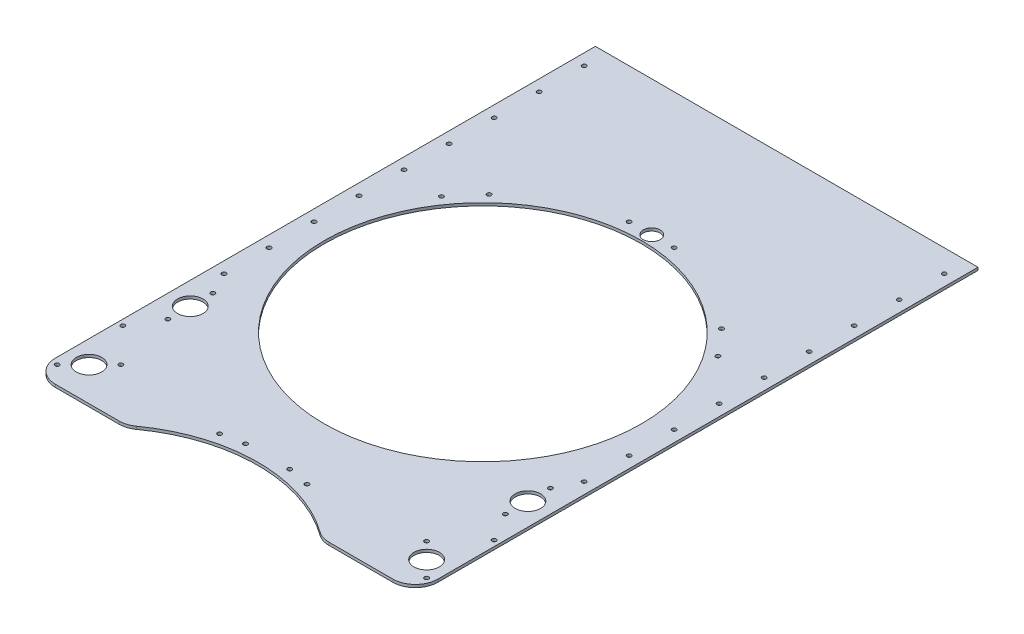
SolidWorks part; units mm, degrees
material "6063-T1"
ref_plane "Front Plane" through (0, 0, 0) normal (0, 0, 1) x (1, 0, 0)
ref_plane "Top Plane" through (0, 0, 0) normal (0, 1, 0) x (1, 0, 0)
ref_plane "Right Plane" through (0, 0, 0) normal (1, 0, 0) x (0, 0, -1)
sketch "Sketch1" plane through (0, 0, 0) normal (0, 1, 0) x (1, 0, 0)
  line L1 (-215.9, 342.9) -> (215.9, 342.9)
  line L2 (-215.9, 342.9) -> (-215.9, -342.9)
  line L3 (-215.9, -342.9) -> (215.9, -342.9)
  line L4 (215.9, 342.9) -> (215.9, -342.9)
  line L5 (-215.9, 342.9) -> (215.9, -342.9) construction
  line L6 (-215.9, -342.9) -> (215.9, 342.9) construction
  point P0 (0, 0)
  dimension "D1" = 431.8
  dimension "D2" = 685.8
extrude "Boss-Extrude1" add sketch "Sketch1" along normal blind 3.175
sketch "Sketch2" plane through (0, 3.175, 0) normal (0, 1, 0) x (1, 0, 0)
  line L0 (0, -342.9) -> (0, 342.9) construction
  line L1 (-215.9, -342.9) -> (215.9, -342.9) construction
  line L2 (215.9, 342.9) -> (-215.9, 342.9) construction
  line L3 (-215.9, 342.9) -> (-215.9, -342.9) construction
  line L4 (-208.4605, -322.7605) -> (-190.5, -304.8) construction
  line L5 (-193.1461, -304.8) -> (-215.9, -304.8) construction
  circle A0 centre (-190.5, -304.8) radius 14.3129
  circle A1 centre (-190.5, -190.5) radius 14.3129
  circle A3 centre (190.5, -190.5) radius 14.3129
  circle A4 centre (190.5, -190.5) radius 25.4 construction
  circle A5 centre (-190.5, -190.5) radius 25.4 construction
  circle A6 centre (190.5, -215.9) radius 2.3813
  circle A7 centre (190.5, -165.1) radius 2.3813
  circle A8 centre (-190.5, -215.9) radius 2.3813
  circle A9 centre (-190.5, -165.1) radius 2.3813
  circle A10 centre (-190.5, -304.8) radius 25.4 construction
  circle A11 centre (-208.4605, -322.7605) radius 2.3813
  circle A15 centre (-172.5395, -286.8395) radius 2.3813
  circle A16 centre (172.5395, -286.8395) radius 2.3813
  circle A17 centre (208.4605, -322.7605) radius 2.3813
  circle A18 centre (190.5, -304.8) radius 14.3129
  point P33 (-190.5, -304.8)
  point P34 (-190.5, -304.8)
  dimension "D1" = 28.6258
  dimension "D2" = 28.6258
  dimension "D6" = 50.8
  dimension "D7" = 50.8
  dimension "D8" = 4.7625
  dimension "D9" = 4.7625
  dimension "D10" = 4.7625
  dimension "D11" = 4.7625
  dimension "D12" = 50.8
  dimension "D13" = 4.7625
  dimension "D3" = 38.1
  dimension "D4" = 114.3
  dimension "D5" = 25.4
  dimension "D15" = 45
  dimension "D14" = 2
extrude "Cut-Extrude1" cut sketch "Sketch2" against normal through all
sketch "Sketch3" plane through (0, 0, 0) normal (0, -1, 0) x (-1, 0, 0)
  line L1 (29.8706, 270.2084) -> (-24.7394, 270.2084)
  line L2 (29.8706, 270.2084) -> (29.8706, 216.2334)
  line L3 (29.8706, 216.2334) -> (-24.7394, 216.2334)
  line L4 (-24.7394, 270.2084) -> (-24.7394, 216.2334)
  line L5 (29.8706, 270.2084) -> (-24.7394, 216.2334) construction
  line L6 (29.8706, 216.2334) -> (-24.7394, 270.2084) construction
  point P0 (2.5656, 243.2209)
  dimension "D1" = 53.975
  dimension "D2" = 54.61
extrude "Boss-Extrude2" [suppressed] add sketch "Sketch3" along normal blind 203.2
fillet "Fillet1" [suppressed] radius 20.32
sketch "Sketch4" [suppressed] plane through (0, -203.2, 0) normal (0, -1, 0) x (-1, 0, 0)
  line L0 (-24.7394, 216.2334) -> (29.8706, 216.2334) construction
  line L1 (26.6956, 267.0334) -> (-21.5644, 267.0334)
  line L2 (26.6956, 267.0334) -> (26.6956, 219.4084)
  line L3 (26.6956, 219.4084) -> (-21.5644, 219.4084)
  line L4 (-21.5644, 267.0334) -> (-21.5644, 219.4084)
  line L5 (26.6956, 267.0334) -> (-21.5644, 219.4084) construction
  line L6 (26.6956, 219.4084) -> (-21.5644, 267.0334) construction
  line L7 (29.8706, 270.2084) -> (-24.7394, 270.2084) construction
  line L8 (29.8706, 216.2334) -> (29.8706, 270.2084) construction
  line L9 (-24.7394, 270.2084) -> (-24.7394, 216.2334) construction
  point P0 (2.5656, 243.2209)
  dimension "D1" = 3.175
  dimension "D2" = 3.175
  dimension "D3" = 3.175
  dimension "D4" = 3.175
extrude "Cut-Extrude2" [suppressed] cut sketch "Sketch4" against normal blind 203.2
sketch "Sketch5" [suppressed] plane through (-29.8706, 0, 0) normal (-1, 0, 0) x (0, 0, 1)
  line L0 (-216.2334, -203.2) -> (-216.2334, 0) construction
  line L1 (-216.2334, -203.2) -> (-270.2084, -203.2) construction
  circle A0 centre (-243.2209, -184.15) radius 14.2875
  dimension "D1" = 28.575
  dimension "D2" = 26.9875
  dimension "D3" = 19.05
extrude "Cut-Extrude3" [suppressed] cut sketch "Sketch5" against normal blind 203.2
sketch "Sketch6" plane through (0, 3.175, 0) normal (0, 1, 0) x (1, 0, 0)
  circle A0 centre (0, -50.8) radius 179.07
  dimension "D1" = 358.14
  dimension "D2" = 50.8
extrude "Cut-Extrude4" cut sketch "Sketch6" against normal through all
sketch "Sketch8" plane through (0, 3.175, 0) normal (0, 1, 0) x (1, 0, 0)
  circle A0 centre (0, 139.7) radius 9.525
  circle A2 centre (0, 139.7) radius 25.4 construction
  circle A3 centre (25.4, 139.7) radius 2.3813
  circle A4 centre (-25.4, 139.7) radius 2.3813
  dimension "D1" = 19.05
  dimension "D3" = 50.8
  dimension "D4" = 4.7625
  dimension "D5" = 4.7625
  dimension "D2" = 139.7
extrude "Cut-Extrude6" cut sketch "Sketch8" against normal through all
fillet "Fillet2" radius 25.4 2 edges at (215.9, 1.5875, 342.9) (-215.9, 1.5875, 342.9)
sketch "Sketch10" plane through (0, 3.175, 0) normal (0, 1, 0) x (1, 0, 0)
  line L0 (-215.9, 342.9) -> (-215.9, -317.5) construction
  line L1 (215.9, -317.5) -> (215.9, 342.9) construction
  circle A0 centre (-190.5, 215.9) radius 14.3129
  circle A1 centre (190.5, 215.9) radius 14.3129
  circle A2 centre (-190.5, 215.9) radius 25.4 construction
  circle A3 centre (190.5, 215.9) radius 25.4 construction
  circle A4 centre (190.5, 190.5) radius 2.3813
  circle A5 centre (190.5, 241.3) radius 2.3813
  circle A6 centre (-190.5, 190.5) radius 2.3813
  circle A7 centre (-190.5, 241.3) radius 2.3813
  circle A8 centre (190.5, -190.5) radius 14.3129 construction
  circle A9 centre (-190.5, -190.5) radius 14.3129 construction
  dimension "D1" = 28.6258
  dimension "D2" = 50.8
  dimension "D3" = 28.6258
  dimension "D4" = 50.8
  dimension "D5" = 4.7625
  dimension "D6" = 4.7625
  dimension "D7" = 4.7625
  dimension "D8" = 4.7625
  dimension "D9" = 25.4
  dimension "D10" = 25.4
  dimension "D11" = 406.4
  dimension "D12" = 406.4
extrude "Cut-Extrude8" [suppressed] cut sketch "Sketch10" against normal through all
sketch "Sketch11" plane through (0, 3.175, 0) normal (0, 1, 0) x (1, 0, 0)
  line L0 (0, -50.8) -> (156.0485, 58.4663) construction
  line L6 (0, 0) -> (0, 139.7) construction
  circle A0 centre (0, -50.8) radius 179.07
  circle A1 centre (0, -50.8) radius 179.07 construction
  circle A2 centre (0, -50.8) radius 184.15
  circle A3 centre (0, -50.8) radius 215.9
  circle A4 centre (156.0485, 58.4663) radius 2.3813
  circle A5 centre (131.1838, 87.3342) radius 2.3813
  circle A6 centre (0, -50.8) radius 190.5 construction
  circle A7 centre (-131.1838, 87.3342) radius 2.3813
  circle A8 centre (-156.0485, 58.4663) radius 2.3813
  dimension "D1" = 368.3
  dimension "D6" = 431.8
  dimension "D7" = 381
  dimension "D9" = 4.7625
  dimension "D10" = 4.7625
  dimension "D2" = 55
  dimension "D8" = 38.1
extrude "Cut-Extrude9" cut sketch "Sketch11" against normal through all contours A4 | A5 | A7 | A8 region at (156.0485, 3.175, -58.4663) region at (131.1838, 3.175, -87.3342) region at (-131.1838, 3.175, -87.3342) region at (-156.0485, 3.175, -58.4663)
sketch "Sketch13" plane through (0, 3.175, 0) normal (0, 1, 0) x (1, 0, 0)
  line L0 (-215.9, 342.9) -> (-215.9, -317.5) construction
  line L1 (215.9, 342.9) -> (-215.9, 342.9) construction
  line L2 (0, -342.9) -> (0, 342.9) construction
  line L3 (-190.5, -342.9) -> (190.5, -342.9) construction
  circle A0 centre (-203.2, 317.5) radius 2.3813
  circle A1 centre (-203.2, 266.7) radius 2.3813
  circle A2 centre (-203.2, 215.9) radius 2.3813
  circle A3 centre (-203.2, 165.1) radius 2.3813
  circle A4 centre (-203.2, 114.3) radius 2.3813
  circle A5 centre (-203.2, 63.5) radius 2.3813
  circle A6 centre (-203.2, 12.7) radius 2.3813
  circle A7 centre (-203.2, -38.1) radius 2.3813
  circle A8 centre (-203.2, -88.9) radius 2.3813
  circle A9 centre (-203.2, -139.7) radius 2.3813
  circle A10 centre (203.2, -139.7) radius 2.3813
  circle A11 centre (203.2, 12.7) radius 2.3813
  circle A12 centre (203.2, 63.5) radius 2.3813
  circle A13 centre (203.2, 114.3) radius 2.3813
  circle A14 centre (203.2, 165.1) radius 2.3813
  circle A15 centre (203.2, 266.7) radius 2.3813
  circle A16 centre (203.2, 317.5) radius 2.3813
  circle A17 centre (-25.4, -330.2) radius 2.4664
  circle A20 centre (-50.8, -330.2) radius 2.3078
  circle A21 centre (50.8, -330.2) radius 2.3078
  circle A22 centre (25.4, -330.2) radius 2.4664
  circle A23 centre (203.2, -88.9) radius 2.3813
  circle A24 centre (203.2, -38.1) radius 2.3813
  circle A25 centre (203.2, 215.9) radius 2.3813
  dimension "D1" = 4.7625
  dimension "D2" = 12.7
  dimension "D3" = 25.4
  dimension "D5" = 25.4
  dimension "D6" = 50.8
  dimension "D7" = 12.7
  dimension "D8" = 12.7
  dimension "D4" = 10
extrude "Cut-Extrude10" cut sketch "Sketch13" against normal through all
sketch "Sketch14" plane through (0, 3.175, 0) normal (0, 1, 0) x (1, 0, 0)
  line L0 (215.9, -317.5) -> (215.9, 342.9) construction
  line L1 (0, -342.9) -> (0, -229.87) construction
  line L2 (-190.5, -342.9) -> (190.5, -342.9) construction
  circle A0 centre (209.55, -247.65) radius 2.3813
  circle A2 centre (0, -50.8) radius 179.07 construction
  circle A3 centre (-209.55, -247.65) radius 2.3813
  circle A4 centre (190.5, -304.8) radius 14.3129 construction
  dimension "D1" = 57.15
  dimension "D3" = 4.7625
  dimension "D2" = 6.35
extrude "Cut-Extrude11" cut sketch "Sketch14" against normal through all
sketch "Sketch16" plane through (0, 3.175, 0) normal (0, 1, 0) x (1, 0, 0)
  line L0 (215.9, -317.5) -> (215.9, 342.9) construction
  line L1 (-215.9, 342.9) -> (215.9, 342.9)
  line L2 (-215.9, 342.9) -> (-215.9, 292.1)
  line L3 (-215.9, 292.1) -> (215.9, 292.1)
  line L4 (215.9, 342.9) -> (215.9, 292.1)
  dimension "D1" = 50.8
extrude "Cut-Extrude13" cut sketch "Sketch16" against normal through all
sketch "Sketch17" plane through (0, 0, 0) normal (0, -1, 0) x (-1, 0, 0)
  line L0 (0, -482.6) -> (0, 3.1553) construction
  line L1 (0, -482.6) -> (24.8652, -293.7298) construction
  line L2 (0, -482.6) -> (49.305, -298.5911) construction
  circle A0 centre (0, -482.6) radius 177.8
  circle A1 centre (0, -482.6) radius 190.5 construction
  circle A2 centre (24.8652, -293.7298) radius 2.3813
  circle A3 centre (49.305, -298.5911) radius 2.3813
  circle A4 centre (-24.8652, -293.7298) radius 2.3813
  circle A5 centre (-49.305, -298.5911) radius 2.3813
  dimension "D1" = 355.6
  dimension "D3" = 381
  dimension "D6" = 4.7625
  dimension "D7" = 4.7625
  dimension "D2" = 482.6
  dimension "D4" = 7.5
  dimension "D5" = 15
extrude "Cut-Extrude14" cut sketch "Sketch17" against normal through all
fillet "Fillet3" radius 25.4 2 edges at (109.9852, 1.5875, 342.9) (-109.9852, 1.5875, 342.9)
